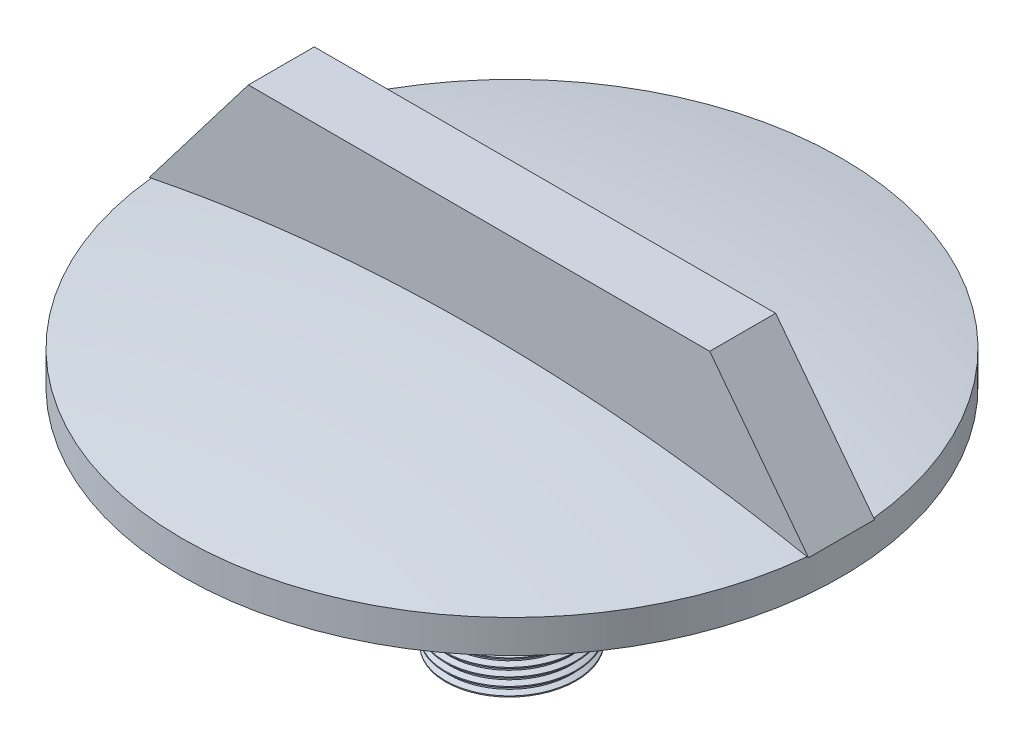
SolidWorks part; units mm, degrees
material "Copper"
ref_plane "Front Plane" through (0, 0, 0) normal (0, 0, 1) x (1, 0, 0)
ref_plane "Top Plane" through (0, 0, 0) normal (0, 1, 0) x (1, 0, 0)
ref_plane "Right Plane" through (0, 0, 0) normal (1, 0, 0) x (0, 0, -1)
sketch "Sketch1" plane through (0, 0, 0) normal (0, 1, 0) x (1, 0, 0)
  circle A0 centre (0, 0) radius 10
extrude "Boss-Extrude1" add sketch "Sketch1" along normal blind 1
sketch "Sketch2" plane through (0, 0, 0) normal (0, 0, 1) x (1, 0, 0)
  line L0 (10, 1) -> (0, 1)
  line L1 (10, 1) -> (-10, 1) construction
  line L2 (0, 1) -> (0, 2)
  arc A0 (0, 2) -> (10, 1) centre (0, -48.5) cw
revolve "Revolve1" add sketch "Sketch2" angle 360 about L2
sketch "Sketch3" plane through (0, 0, 0) normal (0, -1, 0) x (-1, 0, 0)
  circle A0 centre (0, 0) radius 9.5
extrude "Boss-Extrude2" add sketch "Sketch3" along normal blind 0.2
sketch "Sketch4" plane through (0, -0.2, 0) normal (0, -1, 0) x (1, 0, 0)
  circle A0 centre (0, 0) radius 1.98
extrude "Boss-Extrude3" add sketch "Sketch4" along normal blind 7
thread "Thread1" pitch 0.25 method cut profile "Thread Profile1" start angle 0, offset 0, length 6, pitch 0.25, diameter 3.96
ref_plane "Plane1" through (1.98, -7.2, 0) normal (0, 0, 1) x (1, 0, 0)
sketch "Thread Profile1" plane through (1.98, -7.2, 0) normal (0, 0, 1) x (1, 0, 0)
  line L0 (0, 0) -> (0, 0.25) construction
  line L11 (0, 0) -> (0, 0.2187)
  line L12 (0, 0.2187) -> (-0.1353, 0.1406)
  line L13 (-0.1353, 0.1406) -> (-0.1353, 0.0781)
  line L15 (-0.1353, 0.0781) -> (0, 0)
  line L17 (-0.1353, 0.1094) -> (0, 0.1094) construction
  point P2 (0, 0)
  dimension "Pitch" = 0.25
  dimension "Profile_Angle" = 60
  dimension "Profile_Land" = 0.0625
  dimension "Profile_Height" = 0.1353
sketch "Sketch8" plane through (0, 0, 0) normal (0, 0, 1) x (1, 0, 0)
  line L0 (10, 1) -> (7, 4.9254)
  line L5 (-7, 4.9254) -> (7, 4.9254)
  line L6 (-7, 4.9254) -> (-10, 1)
  line L7 (-10, 1) -> (10, 1)
extrude "Boss-Extrude4" add sketch "Sketch8" along normal blind 1 and the other way blind 1
sketch "Sketch9" plane through (0, -7.2, 0) normal (0, -1, 0) x (-1, 0, 0)
  circle A0 centre (0, 0) radius 2.6368
extrude "Cut-Extrude2" cut sketch "Sketch9" against normal blind 0.4
